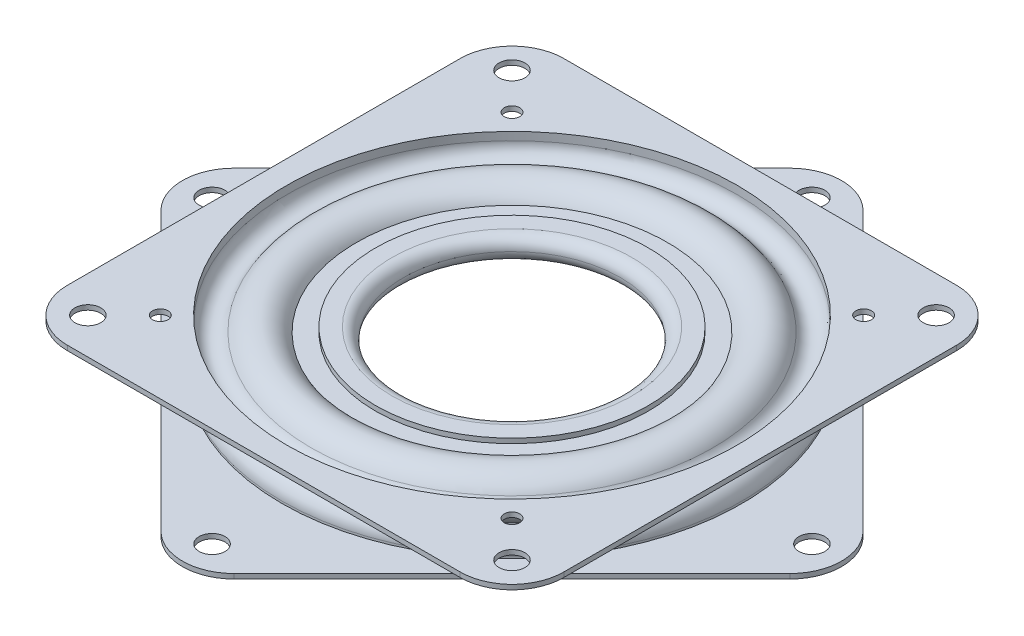
SolidWorks part; units mm, degrees
note: The reader was unsure of these and kept them because the rebuilt part matched: shared geometry of "Sketch1<5>".
ref_plane "Front" through (0, 0, 0) normal (0, 0, 1) x (1, 0, 0)
ref_plane "Top" through (0, 0, 0) normal (0, 1, 0) x (1, 0, 0)
ref_plane "Right" through (0, 0, 0) normal (1, 0, 0) x (0, 0, -1)
sketch "Sketch1" plane through (0, 0, 0) normal (0, 0, 1) x (1, 0, 0)
  line L0 (0, 21.7127) -> (0, -25.7345) construction
  line L1 (20.959, 1.778) -> (18.415, 1.778)
  line L2 (18.415, -1.778) -> (23.503, -1.778)
  line L3 (18.415, 1.0414) -> (23.8727, 1.0414)
  line L4 (34.5578, -3.7655) -> (34.5578, -4.826)
  line L5 (34.5578, -4.826) -> (38.1, -4.826)
  line L6 (-2.2827, 0) -> (4.7936, 0) construction
  line L7 (34.5578, 2.0637) -> (34.5578, 3.302)
  line L8 (34.5578, 3.302) -> (38.1, 3.302)
  arc A0 (18.415, 1.778) -> (18.415, -1.778) centre (18.415, 0) ccw
  arc A1 (23.503, -1.778) -> (30.8363, -2.794) centre (27.3685, -0.8509) ccw
  arc A2 (30.8363, -2.794) -> (34.5578, -3.7655) centre (32.5702, -3.7655) cw
  circle A3 centre (27.3685, -0.8509) radius 3.9751 construction
  arc A4 (23.8727, 1.0414) -> (30.8363, 1.0922) centre (27.3685, -0.8509) cw
  arc A5 (30.8363, 1.0922) -> (34.5578, 2.0637) centre (32.5702, 2.0637) ccw
  point P14 (20.959, -1.778)
  dimension "D1" = 33.274
  dimension "D5" = 7.9502
  dimension "D7" = 3.9751
  dimension "D6" = 54.737
  dimension "D2" = 3.556
  dimension "D3" = 76.2
  dimension "D4" = 6.604
  dimension "D8" = 0.7366
  dimension "D9" = 8.128
revolve "Revolve-Thin4" add sketch "Sketch1" angle 360 about L0
revolve "Revolve-Thin5" add sketch "Sketch1<5>" angle 360 about L0
sketch "Sketch1<5>" plane through (0, 0, 0) normal (0, 0, 1) x (1, 0, 0) same geometry as "Sketch1"
sketch "Sketch2" plane through (0, -4.826, 0) normal (0, -1, 0) x (1, 0, 0)
  line L0 (53.8815, 0) -> (0, -53.8815)
  line L1 (0, -53.8815) -> (-53.8815, 0)
  line L2 (53.8815, 0) -> (0, 53.8815)
  line L3 (0, 53.8815) -> (-53.8815, 0)
  circle A0 centre (0, 0) radius 34.5578
  circle A1 centre (0, 0) radius 34.5578 construction
  circle A4 centre (0, 0) radius 38.1 construction
extrude "Extrude1" add sketch "Sketch2" against normal up to surface (0.7366 mm away) up to face at (0, -4.0894, 38.1)
sketch "Sketch3" plane through (0, 3.302, 0) normal (0, 1, 0) x (-1, 0, 0)
  line L1 (-38.1, -38.1) -> (38.1, -38.1)
  line L2 (-38.1, -38.1) -> (-38.1, 38.1)
  line L3 (-38.1, 38.1) -> (38.1, 38.1)
  line L4 (38.1, -38.1) -> (38.1, 38.1)
  circle A0 centre (0, 0) radius 38.1 construction
  circle A1 centre (0, 0) radius 34.5578
  circle A2 centre (0, 0) radius 34.5578 construction
extrude "Extrude2" add sketch "Sketch3" against normal up to surface (0.7366 mm away) up to face at (0, 2.5654, 38.1)
sketch "Sketch4" plane through (0, 0, 0) normal (0, 0, 1) x (1, 0, 0)
  line L0 (27.3685, 2.5146) -> (27.3685, -4.2164)
  line L1 (26.6717, 2.5146) -> (28.1604, 2.5146) construction
  line L2 (38.1, 2.5654) -> (-38.1, 2.5654) construction
  line L3 (27.3685, 2.8375) -> (27.3685, -4.9447) construction
  arc A0 (27.3685, -4.2164) -> (27.3685, 2.5146) centre (27.3685, -0.8509) ccw
  circle A1 centre (27.3685, -0.8509) radius 3.9751 construction
  dimension "D1" = 0.0508
revolve "Revolve1" add sketch "Sketch4" angle 360 about L3
pattern_circular "CirPattern1" count 3 over 360 about axis through (0, 0, 0) along (0, 1, 0) of bodies 113
fillet "Fillet1" radius 7.9502 4 edges at (-38.1, 2.9337, -38.1) (38.1, 2.9337, -38.1) (-38.1, 2.9337, 38.1) (38.1, 2.9337, 38.1)
fillet "Fillet2" radius 7.9502 4 edges at (53.8815, -4.4577, 0) (0, -4.4577, 53.8815) (0, -4.4577, -53.8815) (-53.8815, -4.4577, 0)
hole_wizard "5/32 (0.156250) Diameter Hole1" positions "Sketch6" profile "Sketch5" hole size "5/32" standard "Ansi Inch" end condition through all
sketch "Sketch6" plane through (0, -4.0894, 0) normal (0, 1, 0) x (-1, 0, 0)
  line L0 (4.6477, -4.6477) -> (-4.6477, 4.6477) construction
  line L1 (4.7889, 4.7889) -> (-4.7889, -4.7889) construction
  line L2 (48.2599, -5.6216) -> (5.6216, -48.2599) construction
  line L3 (-5.6216, -48.2599) -> (-48.2599, -5.6216) construction
  point P0 (0, -46.0328)
  point P1 (-46.0328, 0)
  point P2 (46.0328, 0)
  point P3 (0, 46.0328)
  dimension "D1" = 65.1002
  dimension "D2" = 65.1002
sketch "Sketch5" plane through (0, -4.0894, -46.0328) normal (1, 0, 0) x (0, 0, 1)
  line L0 (0, 0) -> (0, 0.7366)
  line L1 (0, 0.7366) -> (1.9844, 0.7366)
  line L2 (1.9844, 0.7366) -> (1.9844, 0)
  line L5 (1.9844, 0) -> (0, 0)
  line L11 (0, -6.35) -> (0, 107.95) construction
  dimension "Thru Hole Dia." = 3.9688
  dimension "Thru Hole Depth" = 0.7366
hole_wizard "5/32 (0.156250) Diameter Hole2" positions "Sketch8" profile "Sketch7" hole size "5/32" standard "Ansi Inch" end condition through all
sketch "Sketch8" plane through (0, 3.302, 0) normal (0, 1, 0) x (-1, 0, 0)
  line L0 (-7.3126, 0) -> (7.3126, 0) construction
  line L1 (0, 8.4123) -> (0, -8.4123) construction
  point P0 (-32.5501, -32.5501)
  point P5 (32.5501, -32.5501)
  point P7 (32.5501, 32.5501)
  point P8 (-32.5501, 32.5501)
  dimension "D1" = 65.1002
  dimension "D2" = 65.1002
sketch "Sketch7" plane through (32.5501, 3.302, -32.5501) normal (1, 0, 0) x (0, 0, 1)
  line L0 (0, 0) -> (0, 8.128)
  line L1 (0, 8.128) -> (1.9844, 8.128)
  line L2 (1.9844, 8.128) -> (1.9844, 0)
  line L5 (1.9844, 0) -> (0, 0)
  line L11 (0, -6.35) -> (0, 107.95) construction
  dimension "Thru Hole Dia." = 3.9688
  dimension "Thru Hole Depth" = 8.128
hole_wizard "3/32 (0.09375) Diameter Hole1" positions "Sketch10" profile "Sketch9" hole size "3/32" standard "Ansi Inch"
sketch "Sketch10" plane through (0, 3.302, 0) normal (0, 1, 0) x (-1, 0, 0)
  line L0 (12.371, 0) -> (-12.371, 0) construction
  line L1 (0, -6.4329) -> (0, 6.4329) construction
  point P0 (26.9875, -26.9875)
  point P1 (-26.9875, -26.9875)
  point P2 (-26.9875, 26.9875)
  point P3 (26.9875, 26.9875)
  dimension "D1" = 53.975
  dimension "D2" = 53.975
sketch "Sketch9" plane through (-26.9875, 3.302, -26.9875) normal (1, 0, 0) x (0, 0, 1)
  line L0 (0, 0) -> (0, 3.8908)
  line L1 (0, 3.8908) -> (1.1913, 3.175)
  line L2 (1.1913, 3.175) -> (1.1913, 0)
  line L5 (1.1913, 0) -> (0, 0)
  line L10 (0, 3.8908) -> (-1.1913, 3.175) construction
  line L11 (0, -6.35) -> (0, 107.95) construction
  dimension "Hole Dia." = 2.3825
  dimension "Hole Depth" = 3.175
  dimension "Drill Angle" = 118
split line "Split Line1"
equation "\"D7@Sketch1\"=\"D5@Sketch1\"/2"
equation "\"D6@Sketch1\" = (\"D1@Sketch1\"+\"D3@Sketch1\")/2"
